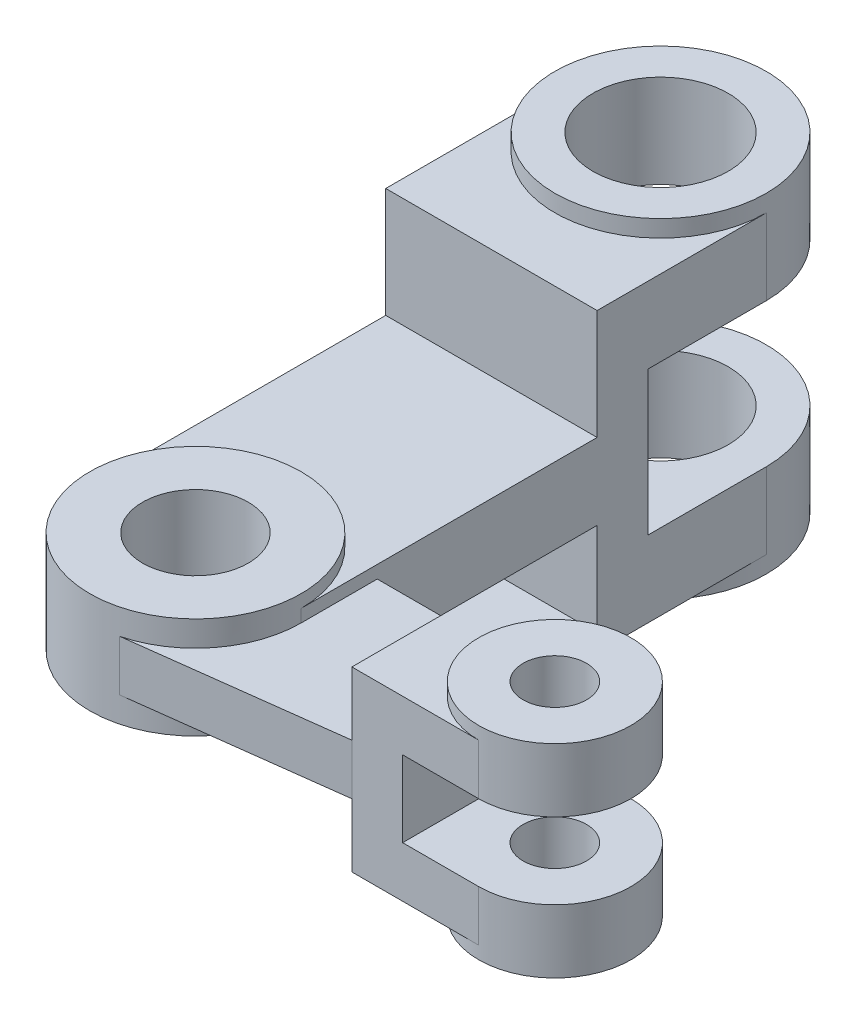
SolidWorks part; units mm, degrees
ref_plane "Front Plane" through (0, 0, 0) normal (1, 0, 0) x (0, 1, 0)
ref_plane "Top Plane" through (0, 0, 0) normal (0, 0, 1) x (0, 1, 0)
ref_plane "Right Plane" through (0, 0, 0) normal (0, 1, 0) x (-1, 0, 0)
sketch "Sketch1" plane through (0, 0, 0) normal (0, 1, 0) x (-1, 0, 0)
  line L0 (-25, 0) -> (-25, 40)
  line L1 (-25, 40) -> (25, 40)
  line L2 (25, 40) -> (25, 0)
  arc A0 (-25, 0) -> (25, 0) centre (0, 0) ccw
  dimension "D1" = 25
  dimension "D2" = 40
extrude "Boss-Extrude2" add sketch "Sketch1" along normal mid plane 70
sketch "Sketch2" plane through (0, 0, 0) normal (1, 0, 0) x (0, 1, 0)
  line L0 (-17, -25) -> (-17, 28)
  line L1 (-35, -25) -> (35, -25) construction
  line L2 (-17, 28) -> (17, 28)
  line L3 (17, 28) -> (17, -25)
  line L4 (17, -25) -> (-17, -25)
  line L5 (35, 40) -> (-35, 40) construction
  point P9 (0, 28)
  dimension "D1" = 12
  dimension "D2" = 34
extrude "Cut-Extrude1" cut sketch "Sketch2" against normal through all both and the other way through all
sketch "Sketch3" plane through (0, 35, 0) normal (0, 1, 0) x (-1, 0, 0)
  circle A0 centre (0, 0) radius 25
  circle A1 centre (0, 0) radius 16
  dimension "D1" = 50
  dimension "D2" = 32
extrude "Boss-Extrude3" add sketch "Sketch3" along normal blind 4
mirror "Mirror1" about plane through (0, 0, 0) normal (0, 1, 0) of "Boss-Extrude3"
sketch "Sketch4" plane through (0, 0, 0) normal (0, 1, 0) x (-1, 0, 0)
  line L0 (-25, 40) -> (25, 40)
  line L1 (25, 40) -> (25, 110)
  line L2 (-25, 110) -> (-25, 40)
  arc A0 (25, 110) -> (-25, 110) centre (0, 110) ccw
  dimension "D1" = 110
extrude "Boss-Extrude4" add sketch "Sketch4" along normal mid plane 18
sketch "Sketch5" plane through (0, 9, 0) normal (0, 1, 0) x (-1, 0, 0)
  circle A0 centre (0, 110) radius 25
  circle A1 centre (0, 110) radius 12.5
  dimension "D1" = 25
extrude "Boss-Extrude5" add sketch "Sketch5" along normal blind 3
mirror "Mirror2" about plane through (0, 0, 0) normal (0, 1, 0) of "Boss-Extrude5"
sketch "Sketch6" plane through (0, 0, 0) normal (0, 1, 0) x (-1, 0, 0)
  line L0 (-85, 128) -> (-55, 128)
  line L1 (-55, 128) -> (-55, 92)
  line L2 (-55, 92) -> (-85, 92)
  arc A0 (-85, 128) -> (-85, 92) centre (-85, 110) ccw
  circle A1 centre (0, 110) radius 25 construction
  dimension "D2" = 36
  dimension "D1" = 85
  dimension "D3" = 30
extrude "Boss-Extrude6" add sketch "Sketch6" along normal mid plane 48 separate body
sketch "Sketch7" plane through (0, 0, 128) normal (0, 0, 1) x (1, 0, 0)
  line L0 (67, 9) -> (67, -9)
  line L1 (67, -9) -> (116.5791, -9)
  line L2 (116.5791, -9) -> (116.5791, 9)
  line L3 (116.5791, 9) -> (67, 9)
  line L4 (55, 24) -> (55, -24) construction
  line L5 (0, 0) -> (125.7248, 0) construction
  dimension "D1" = 12
  dimension "D2" = 18
  dimension "D3" = 49.5791
extrude "Cut-Extrude2" cut sketch "Sketch7" against normal through all both and the other way through all
sketch "Sketch8" plane through (0, 24, 0) normal (0, 1, 0) x (-1, 0, 0)
  line L0 (-85, 128) -> (-55, 128)
  line L1 (-55, 128) -> (-55, 92)
  line L2 (-55, 92) -> (-85, 92)
  line L3 (-85, 110) -> (-62.246, 110) construction
  circle A0 centre (-85, 110) radius 18
  circle A1 centre (-85, 110) radius 7.5
  dimension "D1" = 15
  dimension "D2" = 36
extrude "Cut-Extrude3" cut sketch "Sketch8" against normal through all both and the other way through all contours A1
sketch "Sketch9" plane through (0, 24, 0) normal (0, 1, 0) x (-1, 0, 0)
  line L0 (-85, 128) -> (-55, 128)
  line L1 (-55, 128) -> (-55, 92)
  line L2 (-55, 92) -> (-85, 92)
  arc A0 (-85, 128) -> (-85, 92) centre (-85, 110) cw
  arc A1 (-85, 128) -> (-85, 92) centre (-85, 110) ccw construction
  point P8 (0, 0)
extrude "Cut-Extrude4" cut sketch "Sketch9" against normal blind 3
mirror "Mirror3" about plane through (0, 0, 0) normal (0, 1, 0) of "Cut-Extrude4"
sketch "Sketch11" plane through (0, 0, 0) normal (0, 1, 0) x (-1, 0, 0)
  line L0 (0, 135) -> (-55, 128)
  line L1 (0, 42.9) -> (0, -42.9) construction
  line L2 (-55, 128) -> (-55, 92)
  line L3 (-55, 92) -> (-25, 92)
  line L4 (-25, 110) -> (-25, 40) construction
  line L5 (-25, 92) -> (-25, 110)
  circle A0 centre (0, 110) radius 25 construction
  arc A1 (-25, 110) -> (0, 135) centre (0, 110) cw
extrude "Boss-Extrude8" add sketch "Sketch11" along normal mid plane 12 contours L5 A1 L0 L2 L3 region at (38.2553, 0, 112.2529)
sketch "Sketch12" plane through (0, -35, 0) normal (0, -1, 0) x (1, 0, 0)
  circle A0 centre (0, 0) radius 16
extrude "Cut-Extrude5" cut sketch "Sketch12" against normal through all both and the other way through all
sketch "Sketch13" plane through (0, -9, 0) normal (0, -1, 0) x (1, 0, 0)
  circle A0 centre (0, 110) radius 12.5
extrude "Cut-Extrude6" cut sketch "Sketch13" against normal through all both and the other way through all
